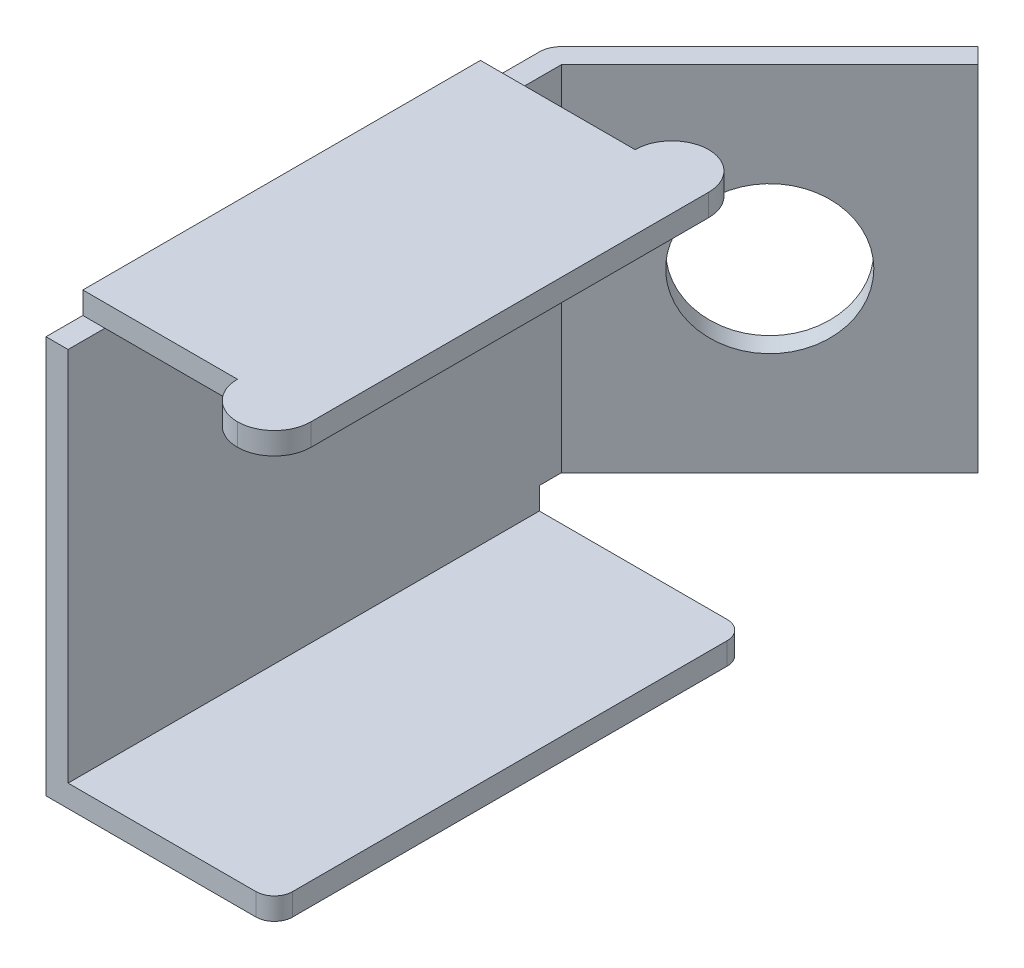
SolidWorks part; units mm, degrees
ref_plane "Front Plane" through (0, 0, 0) normal (0, 0, 1) x (1, 0, 0)
ref_plane "Top Plane" through (0, 0, 0) normal (0, 1, 0) x (1, 0, 0)
ref_plane "Right Plane" through (0, 0, 0) normal (1, 0, 0) x (0, 0, -1)
sketch "Sketch1" plane through (0, 0, 0) normal (0, 1, 0) x (1, 0, 0)
  line L0 (0, -55) -> (0, 55) construction
  line L1 (0, 1.6) -> (1.55, 1.6)
  line L2 (0, 1.6) -> (0, -1.6)
  line L3 (0, -1.6) -> (1.55, -1.6)
  line L4 (1.55, 1.6) -> (1.55, -1.6)
  line L5 (-55, 0) -> (55, 0) construction
  point P6 (0, 0)
  dimension "D1" = 1.55
  dimension "D2" = 3.2
extrude "Boss-Extrude1" add sketch "Sketch1" along normal blind 0.15
fillet "Fillet1" radius 0.125 2 edges at (1.55, 0.075, 1.6) (1.55, 0.075, -1.6)
sketch "Sketch2" plane through (0, 0.15, 0) normal (0, 1, 0) x (1, 0, 0)
  line L0 (1.425, 1.6) -> (0, 1.6) construction
  line L1 (0, 1.6) -> (0.15, 1.6)
  line L2 (0, 1.6) -> (0, -1.6)
  line L3 (0, -1.6) -> (0.15, -1.6)
  line L4 (0.15, 1.6) -> (0.15, -1.6)
  line L5 (0, -1.6) -> (1.425, -1.6) construction
  line L6 (0, -0.0825) -> (0, 0.0825) construction
  dimension "D1" = 0.15
extrude "Boss-Extrude2" add sketch "Sketch2" along normal blind 2.55
sketch "Sketch3" plane through (0, 0, -1.6) normal (0, 0, -1) x (-1, 0, 0)
  line L0 (0, 1.485) -> (0, -1.485) construction
  line L1 (-0.15, 2.7) -> (0, 2.7)
  line L2 (-0.15, 2.7) -> (-0.15, 0.3)
  line L3 (-0.15, 0.3) -> (0, 0.3)
  line L4 (0, 2.7) -> (0, 0.3)
  dimension "D1" = 2.4
extrude "Boss-Extrude3" add sketch "Sketch3" along normal blind 0.15
sketch "Sketch4" plane through (0, 2.7, 0) normal (0, 1, 0) x (1, 0, 0)
  line L0 (0.15, 1.75) -> (1.5642, 3.1642)
  line L1 (1.425, 1.6) -> (0.15, 1.6) construction
  line L2 (1.5642, 3.1642) -> (1.4581, 3.2703)
  line L3 (0.15, 1.75) -> (0.0439, 1.8561) construction
  line L6 (1.4581, 3.2703) -> (0.0439, 1.8561)
  line L7 (0.15, 1.75) -> (0, 1.75)
  line L9 (0, -1.485) -> (0, 1.485) construction
  line L10 (0, 1.75) -> (0.15, 1.75) construction
  arc A0 (0.0439, 1.8561) -> (0, 1.75) centre (0.15, 1.75) ccw
  dimension "D1" = 45
  dimension "D2" = 2
  dimension "D3" = 0.15
  dimension "D4" = 0.15
extrude "Boss-Extrude4" add sketch "Sketch4" against normal blind 2.4
sketch "Sketch5" plane through (-0.8, 0, -0.8) normal (0.7071, 0, 0.7071) x (0.7071, 0, -0.7071)
  line L0 (1.3435, 2.7) -> (3.3435, 0.3) construction
  line L1 (1.3435, 0.3) -> (3.3435, 2.7) construction
  circle A0 centre (2.3435, 1.5) radius 0.5
  dimension "D1" = 1
extrude "Cut-Extrude1" cut sketch "Sketch5" against normal through all
sketch "Sketch6" plane through (0, 2.7, 0) normal (0, 1, 0) x (1, 0, 0)
  line L0 (0, -1.485) -> (0, 1.485) construction
  line L1 (0, -1.35) -> (1.05, -1.35)
  line L2 (0, -1.35) -> (0, 1.35)
  line L3 (0, 1.35) -> (1.05, 1.35)
  line L4 (1.05, -1.35) -> (1.05, 1.35)
  line L5 (-0.8603, 0) -> (0.8603, 0) construction
  line L6 (0.15, -1.6) -> (1.425, -1.6) construction
  line L7 (1.55, -1.475) -> (1.55, 1.475) construction
  point P6 (0, 0)
  dimension "D1" = 0.25
  dimension "D2" = 0.5
extrude "Boss-Extrude5" add sketch "Sketch6" along normal blind 0.15
sketch "Sketch7" plane through (0, 2.85, 0) normal (0, 1, 0) x (1, 0, 0)
  line L0 (0.15, -1.6) -> (1.425, -1.6) construction
  line L1 (1.55, -1.6) -> (1.05, -1.6)
  line L2 (1.55, -1.6) -> (1.55, 1.6)
  line L3 (1.55, 1.6) -> (1.05, 1.6)
  line L4 (1.05, -1.6) -> (1.05, 1.6)
  line L5 (1.425, 1.6) -> (0.15, 1.6) construction
  line L6 (1.05, -1.35) -> (1.05, 1.35) construction
  line L7 (1.55, -1.475) -> (1.55, 1.475) construction
extrude "Boss-Extrude6" add sketch "Sketch7" against normal blind 0.15
fillet "Fillet2" radius 0.25 4 edges at (1.05, 2.775, -1.6) (1.55, 2.775, -1.6) (1.05, 2.775, 1.6) (1.55, 2.775, 1.6)
